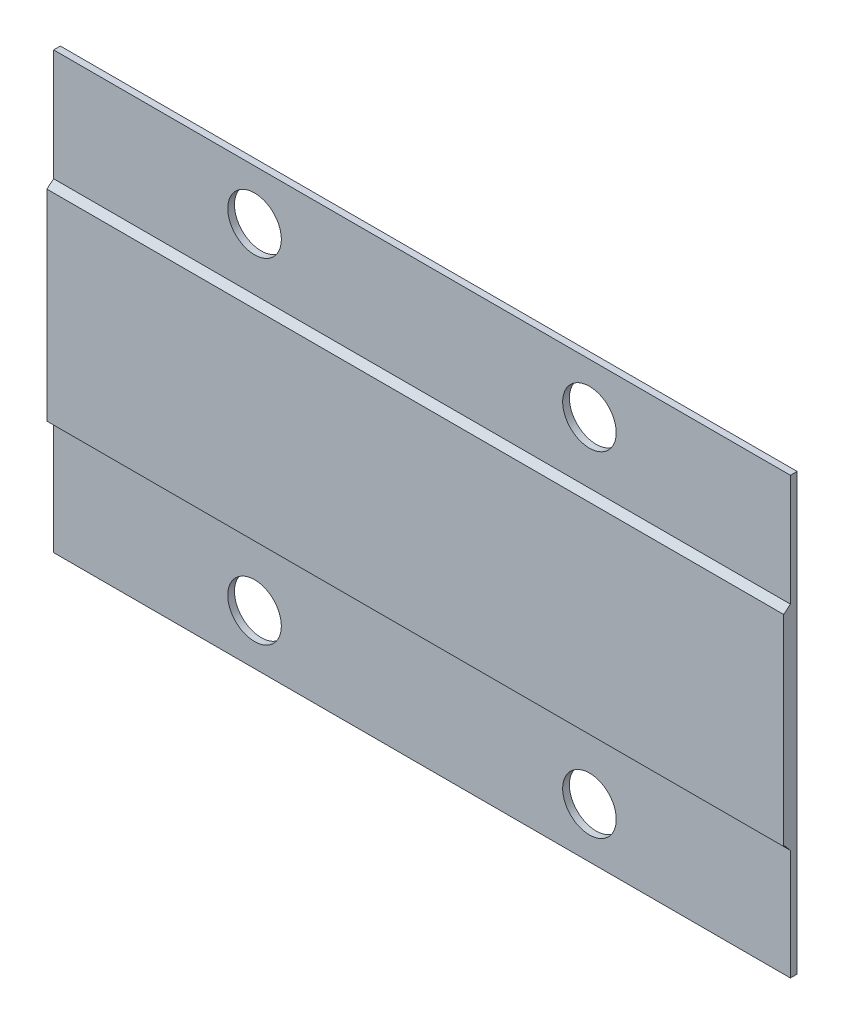
SolidWorks part; units mm, degrees
ref_plane "Front Plane" through (0, 0, 0) normal (0, 0, 1) x (1, 0, 0)
ref_plane "Top Plane" through (0, 0, 0) normal (0, 1, 0) x (1, 0, 0)
ref_plane "Right Plane" through (0, 0, 0) normal (1, 0, 0) x (0, 0, -1)
sketch "Sketch1" plane through (0, 0, 0) normal (0, 0, 1) x (1, 0, 0)
  line L0 (12, 23) -> (32, 23) construction
  line L1 (0, 0) -> (44, 0)
  line L2 (0, 0) -> (0, 26)
  line L3 (0, 26) -> (44, 26)
  line L4 (44, 0) -> (44, 26)
  line L5 (32, 23) -> (32, 3) construction
  line L6 (32, 3) -> (12, 3) construction
  line L7 (12, 3) -> (12, 23) construction
  circle A0 centre (12, 23) radius 1.6
  circle A1 centre (32, 23) radius 1.6
  circle A2 centre (12, 3) radius 1.6
  circle A3 centre (32, 3) radius 1.6
  point P13 (22, 23)
  point P14 (22, 26)
  point P15 (32, 13)
  point P16 (44, 13)
  dimension "D3" = 20
  dimension "D4" = 3.2
  dimension "D1" = 26
  dimension "D2" = 44
extrude "Boss-Extrude1" add sketch "Sketch1" along normal blind 0.4 contours L1 L4 L3 L2 A3 A2 A1 A0 region at (22, 13, 0)
sketch "Sketch2" plane through (0, 0, 0.4) normal (0, 0, 1) x (1, 0, 0)
  line L0 (44, 0) -> (44, 26) construction
  line L1 (0, 19) -> (44, 19)
  line L2 (0, 19) -> (0, 7)
  line L3 (0, 7) -> (44, 7)
  line L4 (44, 19) -> (44, 7)
  line L5 (0, 0) -> (0, 26) construction
  point P4 (44, 13)
  point P7 (44, 13)
  point P8 (0, 6.5551)
  line M7 (44, 0) -> (44, 26)
  line M9 (0, 26) -> (0, 0)
  dimension "D1" = 12
extrude "Boss-Extrude2" add sketch "Sketch2" along normal blind 0.4 contours L3 L1 M9 M7 region at (22, 13, 0.4)
chamfer "Chamfer1" distance 0.4 angle 40 2 edges at (22, 7, 0.4) (22, 19, 0.4) first distance on face at (22, 3.5, 0.4) first distance on face at (22, 19, 0.6)
